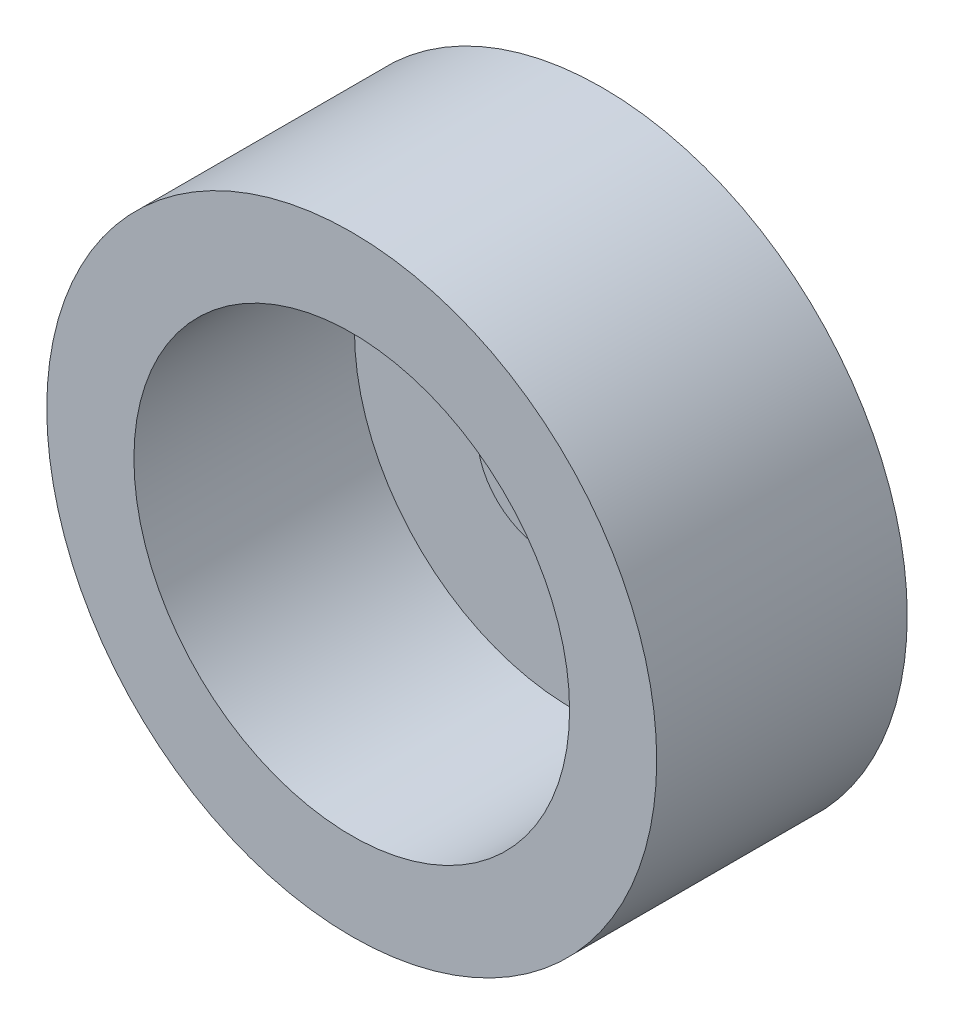
SolidWorks part; units mm, degrees
ref_plane "Alzado" through (0, 0, 0) normal (0, 0, 1) x (1, 0, 0)
ref_plane "Planta" through (0, 0, 0) normal (0, 1, 0) x (1, 0, 0)
ref_plane "Vista lateral" through (0, 0, 0) normal (1, 0, 0) x (0, 0, -1)
sketch "Croquis1" plane through (0, 0, 0) normal (0, 0, 1) x (1, 0, 0)
  circle A0 centre (0, 0) radius 56
  dimension "D1" = 112
extrude "Saliente-Extruir1" add sketch "Croquis1" along normal mid plane 46
sketch "Croquis2" plane through (0, 0, 23) normal (0, 0, 1) x (1, 0, 0)
  circle A0 centre (0, 0) radius 40
  dimension "D1" = 80
extrude "Cortar-Extruir1" cut sketch "Croquis2" against normal blind 40.5
sketch "Croquis3" plane through (0, 0, -17.5) normal (0, 0, 1) x (1, 0, 0)
  circle A0 centre (0, 0) radius 12.5
  dimension "D1" = 25
extrude "Saliente-Extruir2" add sketch "Croquis3" along normal blind 5
sketch "Croquis4" plane through (0, 0, -12.5) normal (0, 0, 1) x (1, 0, 0)
  line L1 (0, 9.815) -> (-8.5, 4.9075)
  line L2 (-8.5, 4.9075) -> (-8.5, -4.9075)
  line L3 (-8.5, -4.9075) -> (0, -9.815)
  line L4 (0, -9.815) -> (8.5, -4.9075)
  line L5 (8.5, -4.9075) -> (8.5, 4.9075)
  line L6 (8.5, 4.9075) -> (0, 9.815)
  circle A0 centre (0, 0) radius 8.5 construction
  point P1 (0, 0)
  point P11 (8.5, -5.1213)
  dimension "D1" = 17
extrude "Cortar-Extruir2" cut sketch "Croquis4" against normal blind 5
sketch "Croquis5" plane through (0, 0, -17.5) normal (0, 0, 1) x (1, 0, 0)
  circle A0 centre (0, 0) radius 6
  dimension "D1" = 12
extrude "Cortar-Extruir3" cut sketch "Croquis5" against normal through all
ref_axis "Eje1" through (0, 0, -23) along (0, 0, 1)
sketch "Croquis6" plane through (0, 0, -23) normal (0, 0, -1) x (-1, 0, 0)
  circle A0 centre (0, 0) radius 12.5
  dimension "D1" = 25
extrude "Cortar-Extruir4" cut sketch "Croquis6" against normal blind 3
